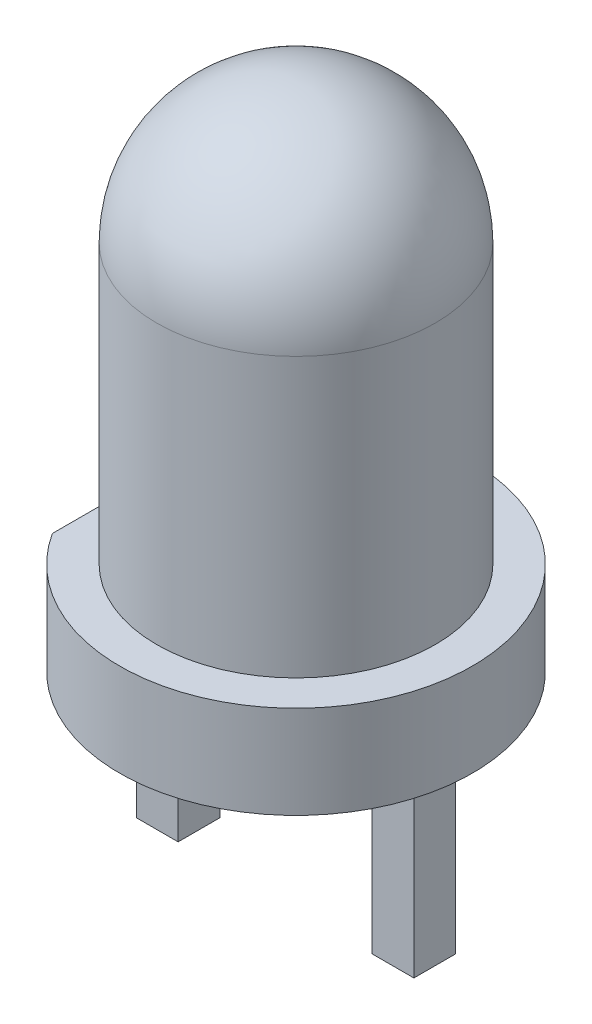
SolidWorks part; units mm, degrees
ref_plane "Front Plane" through (0, 0, 0) normal (0, 0, 1) x (1, 0, 0)
ref_plane "Top Plane" through (0, 0, 0) normal (0, 1, 0) x (1, 0, 0)
ref_plane "Right Plane" through (0, 0, 0) normal (1, 0, 0) x (0, 0, -1)
sketch "Sketch2" plane through (0, 0, 0) normal (1, 0, 0) x (0, 0, -1)
  line L0 (1.045, -1.8) -> (1.495, -1.8)
  line L1 (1.495, -1.8) -> (1.495, 1.09)
  line L2 (1.495, 1.09) -> (1.395, 1.19)
  line L3 (1.395, 1.19) -> (1.395, 2.39)
  line L4 (1.395, 2.39) -> (-0.795, 2.39)
  line L5 (-0.795, 2.39) -> (-0.795, 1.99)
  line L6 (-0.795, 1.99) -> (0.005, 1.19)
  line L7 (0.005, 1.19) -> (0.755, 1.19)
  line L8 (0.755, 1.19) -> (1.045, 0.9)
  line L9 (1.045, 0.9) -> (1.045, -1.8)
  line L10 (-1.495, -1.8) -> (-1.045, -1.8)
  line L11 (-1.045, -1.8) -> (-1.045, 0.9)
  line L12 (-1.045, 0.9) -> (-0.755, 1.19)
  line L13 (-0.755, 1.19) -> (-0.495, 1.19)
  line L14 (-0.495, 1.19) -> (-0.495, 1.39)
  line L15 (-0.495, 1.39) -> (-1.095, 1.99)
  line L16 (-1.095, 1.99) -> (-1.095, 2.39)
  line L17 (-1.095, 2.39) -> (-1.395, 2.39)
  line L18 (-1.395, 2.39) -> (-1.395, 1.19)
  line L19 (-1.395, 1.19) -> (-1.495, 1.09)
  line L20 (-1.495, 1.09) -> (-1.495, -1.8)
  line L21 (0, 0) -> (0, 50000) construction
  point P3 (0.9548, -1.2613)
  point P13 (-1.27, -1.8)
  point P24 (1.27, -1.8)
  point P25 (-1.495, 2.8635)
  point P26 (-1.395, 3.013)
  dimension "D1" = 2.54
  dimension "D2" = 0.45
  dimension "D3" = 2.7
  dimension "D4" = 0.29
  dimension "D5" = 135
  dimension "D6" = 0.1
  dimension "D7" = 0.3
  dimension "D8" = 1.2
  dimension "D9" = 0.75
  dimension "D10" = 0.55
  dimension "D11" = 0.3
  dimension "D12" = 1.8
extrude "Boss-Extrude1" add sketch "Sketch2" along normal mid plane 0.45
sketch "Sketch3" plane through (0, 0, 0) normal (1, 0, 0) x (0, 0, -1)
  line L0 (0, 0) -> (0, 50000) construction
  line L1 (0, 2.39) -> (0.685, 2.39)
  line L2 (1.395, 2.39) -> (-0.795, 2.39) construction
  line L3 (0.6945, 2.3634) -> (0, 1.79)
  line L4 (0, 1.79) -> (0, 2.39)
  line L5 (0, 2.09) -> (0.6, 2.39)
  arc A0 (0.685, 2.39) -> (0.6945, 2.3634) centre (0.685, 2.375) cw
  point P10 (0.7267, 2.39)
  dimension "D1" = 0.015
  dimension "D2" = 0.7
  dimension "D3" = 0.6
  dimension "D4" = 0.3
  dimension "D5" = 0.6
revolve "Revolve1" add sketch "Sketch3" angle 360 about L0 region at (0, 2.29, -0.2) region at (0, 2.119, -0.2707)
revolve "Cut-Revolve1" cut sketch "Sketch3<5>" angle 360 about L0 region at (0, 2.29, -0.2)
sketch "Sketch3<5>" plane through (0, 0, 0) normal (1, 0, 0) x (0, 0, -1) same geometry as "Sketch3"
sketch "Sketch5" plane through (0, 2.39, 0) normal (0, 1, 0) x (1, 0, 0)
  line L1 (-0.15, -0.15) -> (0.15, -0.15)
  line L2 (-0.15, -0.15) -> (-0.15, 0.15)
  line L3 (-0.15, 0.15) -> (0.15, 0.15)
  line L4 (0.15, -0.15) -> (0.15, 0.15)
  line L5 (-0.15, -0.15) -> (0.15, 0.15) construction
  line L6 (-0.15, 0.15) -> (0.15, -0.15) construction
  point P0 (0, 0)
  dimension "D1" = 0.3
extrude "Boss-Extrude2" add sketch "Sketch5" along normal blind 0.1 and the other way up to body separate body
sketch "Sketch6" plane through (0, 0, 0) normal (1, 0, 0) x (0, 0, -1)
  line L0 (0, 0) -> (0, 50000) construction
  line L1 (0, 0.2) -> (1.9, 0.2)
  line L2 (1.9, 0.2) -> (1.9, 1.2)
  line L3 (1.9, 1.2) -> (1.5, 1.2)
  line L4 (1.5, 1.2) -> (1.5, 4.2)
  line L5 (0, 5.7) -> (0, 0.2)
  line L6 (1.045, -1.8) -> (1.495, -1.8) construction
  arc A0 (1.5, 4.2) -> (0, 5.7) centre (0, 4.2) ccw
  dimension "D4" = 1.5
  dimension "D1" = 1
  dimension "D2" = 1.9
  dimension "D3" = 3
  dimension "D5" = 3
  dimension "D6" = 2
revolve "Revolve2" add sketch "Sketch6" angle 360 about L0
sketch "Sketch7" plane through (0, 0.2, 0) normal (0, -1, 0) x (1, 0, 0)
  line L0 (-1.0247, -1.6) -> (1.0247, -1.6)
  line L1 (0.225, -1.495) -> (-0.225, -1.495) construction
  circle A0 centre (0, 0) radius 1.9 construction
  arc A2 (-1.0247, -1.6) -> (1.0247, -1.6) centre (0, 0) ccw
  dimension "D1" = 1.6
extrude "Cut-Extrude1" cut sketch "Sketch7" against normal up to surface (1 mm away) up to face at (0, 1.2, -1.5)
move or copy body "Body-Move/Copy1" bodies to move or copy 102 111 106 copy no rotation origin (0, 0, 0) rotation axis (0, 1, 0) rotation angle 90
